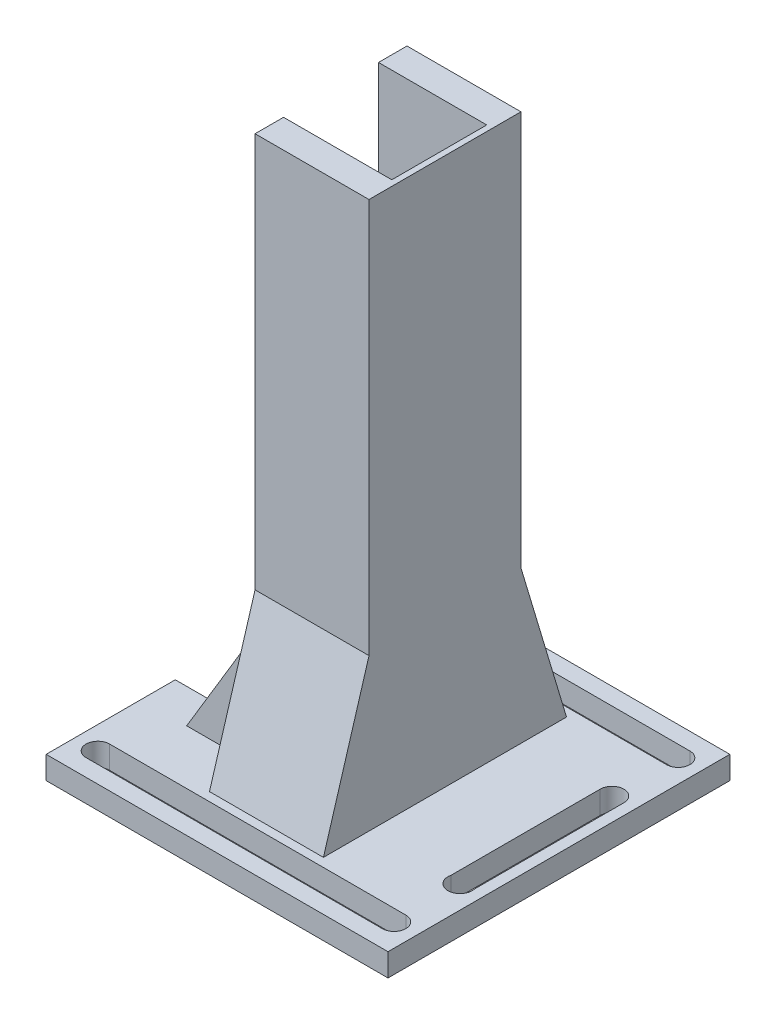
SolidWorks part; units mm, degrees
ref_plane "前视基准面" through (0, 0, 0) normal (0, 0, 1) x (1, 0, 0)
ref_plane "上视基准面" through (0, 0, 0) normal (0, 1, 0) x (1, 0, 0)
ref_plane "右视基准面" through (0, 0, 0) normal (1, 0, 0) x (0, 0, -1)
other "Configuration Table"
sketch "草图1" plane through (0, 0, 0) normal (0, 1, 0) x (1, 0, 0)
  line L1 (-45, 45) -> (45, 45)
  line L2 (-45, 45) -> (-45, -45)
  line L3 (-45, -45) -> (45, -45)
  line L4 (45, 45) -> (45, -45)
  line L5 (-45, 45) -> (45, -45) construction
  line L6 (-45, -45) -> (45, 45) construction
  point P0 (0, 0)
  dimension "D1" = 90
  dimension "D2" = 90
extrude "凸台-拉伸1" add sketch "草图1" along normal blind 6
sketch "草图2" plane through (0, 0, 0) normal (0, 1, 0) x (1, 0, 0)
  line L1 (-15, 20) -> (15, 20)
  line L2 (-15, 20) -> (-15, -20)
  line L3 (-15, -20) -> (15, -20)
  line L4 (15, 20) -> (15, -20)
  line L5 (-15, 20) -> (15, -20) construction
  line L6 (-15, -20) -> (15, 20) construction
  point P0 (0, 0)
  dimension "D1" = 30
  dimension "D2" = 40
extrude "凸台-拉伸2" add sketch "草图2" along normal blind 150
sketch "草图7" plane through (0, 0, 0) normal (0, 0, 1) x (1, 0, 0)
  line L0 (-15, 36) -> (-33, 6)
  line L1 (-15, 150) -> (-15, 6) construction
  line L2 (-45, 6) -> (45, 6) construction
  line L3 (-33, 6) -> (-15, 6)
  line L4 (-15, 6) -> (-15, 36)
  dimension "D1" = 18
  dimension "D2" = 30
extrude "凸台-拉伸3" add sketch "草图7" along normal up to surface and the other way up to surface up to face at (0, 78, 20) other way up to face at (0, 78, -20)
sketch "草图8" plane through (0, 0, 0) normal (0, 1, 0) x (1, 0, 0)
  line L0 (45, 45) -> (-45, 45) construction
  line L1 (-45, 45) -> (-45, -45) construction
  circle A0 centre (-39, 37.4) radius 3.1
  dimension "D2" = 6.2
  dimension "D1" = 7.6
  dimension "D3" = 6
extrude "切除-拉伸2" cut sketch "草图8" along normal up to surface (6 mm away) up to face at (0, 6, 0)
sketch "草图15" plane through (0, 0, 0) normal (1, 0, 0) x (0, 0, -1)
  line L1 (-20, 46) -> (-20, 6)
  line L6 (-20, 46) -> (-32, 6)
  line L7 (-20, 150) -> (-20, 6) construction
  line L12 (-45, 6) -> (45, 6) construction
  line L13 (-32, 6) -> (-20, 6)
  dimension "D1" = 12
  dimension "D2" = 40
extrude "凸台-拉伸4" add sketch "草图15" along normal blind 15 and the other way blind 15
mirror "镜向11" about plane through (0, 0, 0) normal (0, 0, 1) of "凸台-拉伸4"
sketch "草图17" plane through (0, 0, 0) normal (1, 0, 0) x (0, 0, -1)
  line L0 (-20, 150) -> (-20, 46) construction
  line L1 (12.5, 150) -> (-12.5, 150)
  line L2 (12.5, 150) -> (12.5, 6)
  line L3 (12.5, 6) -> (-12.5, 6)
  line L4 (-12.5, 150) -> (-12.5, 6)
  line L5 (20, 150) -> (20, 46) construction
  line L6 (32, 6) -> (-32, 6) construction
  line L7 (-20, 150) -> (20, 150) construction
  line L8 (-45, 0) -> (45, 0) construction
  dimension "D1" = 25
  dimension "D2" = 7.5
  dimension "D3" = 7.5
  dimension "D4" = 0
  dimension "D5" = 0
  dimension "D6" = 144
  dimension "D7" = 6
extrude "切除-拉伸4" cut sketch "草图17" against normal through all and the other way blind 13.5
sketch "草图21" plane through (0, 0, 0) normal (1, 0, 0) x (0, 0, -1)
  line L0 (-11, 6) -> (11, 6)
  line L1 (32, 6) -> (-32, 6) construction
  line L2 (11, 6) -> (11, 0)
  line L3 (-45, 0) -> (45, 0) construction
  line L4 (11, 0) -> (-11, 0)
  line L5 (-11, 0) -> (-11, 6)
  line L6 (-20, 150) -> (-20, 46) construction
  line L7 (20, 150) -> (20, 46) construction
  dimension "D1" = 22
  dimension "D2" = 9
  dimension "D3" = 9
extrude "切除-拉伸8" cut sketch "草图21" against normal through all and the other way blind 9.5
mirror "镜向12" about plane through (0, 0, 0) normal (1, 0, 0) of "切除-拉伸2"
sketch "草图23" plane through (0, 0, 0) normal (0, 1, 0) x (1, 0, 0)
  line L0 (-39, 40.5) -> (39, 40.5)
  line L1 (39, 40.5) -> (39, 34.3)
  line L2 (39, 34.3) -> (-39, 34.3)
  line L3 (-39, 34.3) -> (-39, 40.5)
  circle A0 centre (-39, 37.4) radius 3.1 construction
  circle A1 centre (39, 37.4) radius 3.1 construction
extrude "切除-拉伸9" cut sketch "草图23" along normal through all
mirror "镜向13" about plane through (0, 0, 0) normal (0, 0, 1) of "切除-拉伸9"
mirror "镜向14" about plane through (0, 0, 0) normal (0, 0, 1) of "镜向12"
sketch "草图25" plane through (0, 0, 0) normal (0, 1, 0) x (1, 0, 0)
  line L0 (42.1, 20) -> (42.1, -20)
  line L1 (42.1, -20) -> (35.8707, -20)
  line L2 (35.8707, -20) -> (35.8707, 20)
  line L3 (35.8707, 20) -> (42.1, 20)
  line L4 (-45, -45) -> (45, -45) construction
  dimension "D1" = 40
  dimension "D2" = 25
extrude "切除-拉伸10" cut sketch "草图25" along normal through all
sketch "草图26" plane through (0, 0, 0) normal (0, 1, 0) x (1, 0, 0)
  line L0 (35.8707, 20) -> (42.1, 20) construction
  circle A0 centre (38.9854, 20) radius 3.1146
extrude "切除-拉伸11" cut sketch "草图26" along normal through all
sketch "草图27" plane through (0, 0, 0) normal (0, 1, 0) x (1, 0, 0)
  line L0 (42.1, -20) -> (35.8707, -20) construction
  circle A0 centre (38.9854, -20) radius 3.2023
extrude "切除-拉伸12" cut sketch "草图27" along normal through all
